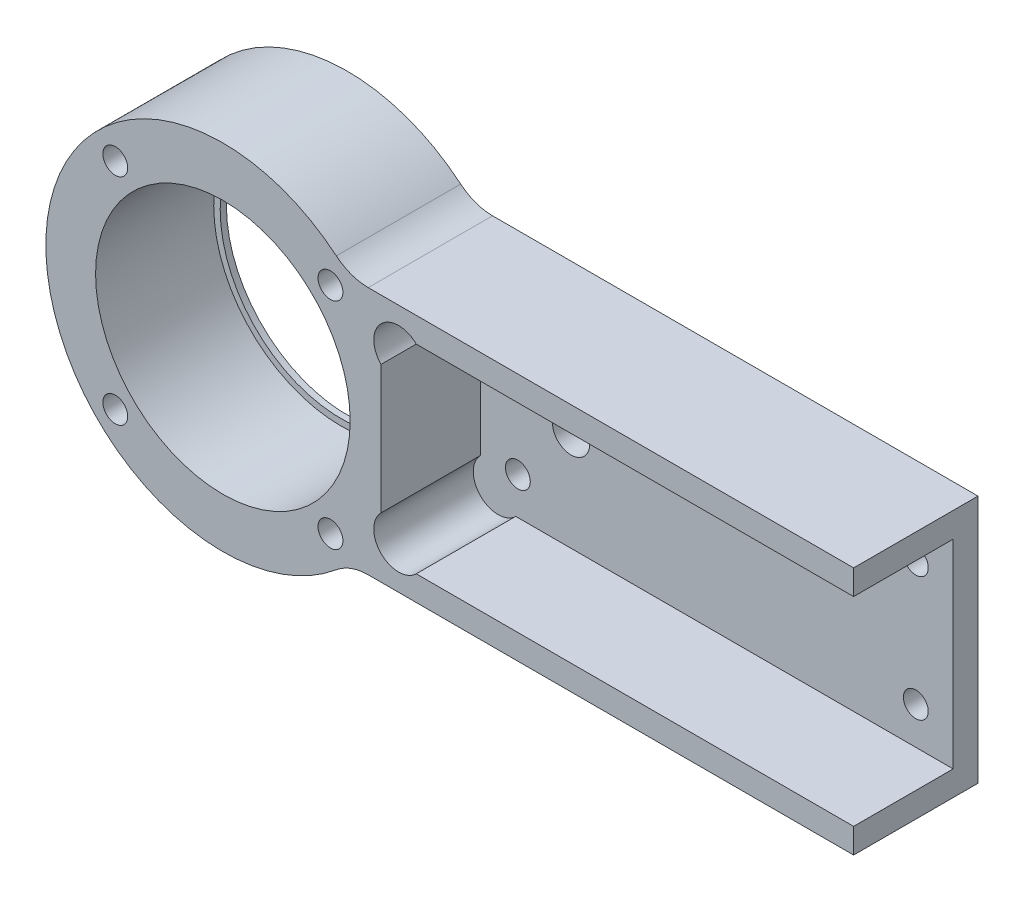
SolidWorks part; units mm, degrees
material "1060 Alloy"
ref_plane "Front Plane" through (0, 0, 0) normal (0, 0, 1) x (1, 0, 0)
ref_plane "Top Plane" through (0, 0, 0) normal (0, 1, 0) x (1, 0, 0)
ref_plane "Right Plane" through (0, 0, 0) normal (1, 0, 0) x (0, 0, -1)
sketch "Sketch1" plane through (0, 0, 0) normal (0, 0, 1) x (1, 0, 0)
  line L0 (32.1711, 31.75) -> (161.036, 31.75)
  line L1 (32.1711, -31.75) -> (161.036, -31.75)
  line L3 (161.036, 31.75) -> (161.036, 25.4)
  line L4 (161.036, -31.75) -> (161.036, -25.4)
  line L5 (161.036, 31.75) -> (161.036, -31.75) construction
  line L6 (161.036, 25.4) -> (40.386, 25.4)
  line L7 (40.386, 25.4) -> (40.386, -25.4)
  line L8 (40.386, -25.4) -> (161.036, -25.4)
  line L9 (161.036, 25.4) -> (161.036, -25.4)
  circle A0 centre (0, 0) radius 32.5
  arc A1 (32.1711, 31.75) -> (32.1711, -31.75) centre (0, 0) ccw
  point P3 (161.036, 0)
  dimension "D1" = 65
  dimension "D4" = 12.7
  dimension "D6" = 40.386
  dimension "D2" = 63.5
  dimension "D3" = 120.65
  dimension "D5" = 6.35
extrude "Boss-Extrude2" add sketch "Sketch1" along normal blind 6.35 contours L0 A1 L1 L4 L8 L7 L6 L3 A0 | L9 L6 L7 L8 region at (33.1354, 0, 0) region at (100.711, 0, 0)
extrude "Boss-Extrude3" add sketch "Sketch1<3>" along normal blind 25.4 from surface contours L0 A1 L1 L4 L8 L7 L6 L3 A0 region at (33.1354, 0, 0) starting at face at (77.2608, 0, 6.35)
sketch "Sketch1<3>" plane through (0, 0, 0) normal (0, 0, 1) x (1, 0, 0) same geometry as "Sketch1"
sketch "Sketch2" plane through (0, 0, 6.35) normal (0, 0, 1) x (1, 0, 0)
  line L0 (161.036, -25.4) -> (161.036, 25.4) construction
  line L1 (40.386, -25.4) -> (40.386, 25.4) construction
  line L2 (-27.4711, 27.4711) -> (0, 0) construction
  line L3 (0, 0) -> (-27.4711, -27.4711) construction
  line L4 (40.386, 25.4) -> (161.036, 25.4) construction
  line L5 (40.386, 25.4) -> (161.036, 25.4) construction
  line L6 (161.036, -25.4) -> (40.386, -25.4) construction
  line L7 (161.036, -25.4) -> (40.386, -25.4) construction
  line L8 (0, 0) -> (27.4711, 27.4711) construction
  line L11 (0, 0) -> (27.4711, -27.4711) construction
  line L13 (0, 0) -> (-32.5, 0) construction
  circle A0 centre (49.911, 15.875) radius 3.175
  circle A1 centre (151.511, 15.875) radius 3.175
  circle A2 centre (151.511, -15.875) radius 3.175
  circle A3 centre (49.911, -15.875) radius 3.175
  circle A4 centre (27.4711, 27.4711) radius 3.175
  circle A5 centre (27.4711, -27.4711) radius 3.175
  circle A6 centre (-27.4711, -27.4711) radius 3.175
  circle A7 centre (-27.4711, 27.4711) radius 3.175
  circle A8 centre (0, 0) radius 32.5 construction
  circle A15 centre (0, 0) radius 38.85 construction
  arc A16 (32.1711, 31.75) -> (32.1711, -31.75) centre (0, 0) ccw construction
  dimension "D1" = 6.35
  dimension "D2" = 6.35
  dimension "D4" = 9.525
  dimension "D5" = 9.525
  dimension "D6" = 9.525
  dimension "D3" = 9.525
  dimension "D7" = 9.525
  dimension "D8" = 9.525
  dimension "D11" = 45
  dimension "D12" = 45
extrude "Cut-Extrude1" cut sketch "Sketch2" against normal through all and the other way through all
sketch "Sketch3" plane through (0, 0, 31.75) normal (0, 0, 1) x (1, 0, 0)
  line L0 (40.386, 25.4) -> (49.3663, 16.4197) construction
  line L1 (40.386, 25.4) -> (161.036, 25.4) construction
  line L2 (40.386, 0) -> (32.5, 0) construction
  line L3 (40.386, -25.4) -> (40.386, 25.4) construction
  circle A0 centre (44.8761, 20.9099) radius 6.35
  circle A1 centre (0, 0) radius 32.5 construction
  circle A2 centre (44.8761, -20.9099) radius 6.35
  dimension "D1" = 12.7
  dimension "D2" = 45
extrude "Cut-Extrude2" cut sketch "Sketch3" against normal up to surface (25.4 mm away) up to face at (53.086, 15.875, 6.35)
sketch "Sketch4" plane through (0, 0, 0) normal (0, 0, -1) x (-1, 0, 0)
  line L0 (-31.75, 54.9926) -> (0, 0) construction
  line L1 (0, 0) -> (31.75, 54.9926) construction
  line L2 (-32.1711, -31.75) -> (-161.036, -31.75) construction
  line L3 (0, 0) -> (63.5, 0) construction
  line L4 (0, 0) -> (31.75, -54.9926) construction
  line L9 (-51.2937, 31.75) -> (-32.1711, 31.75)
  line L10 (-32.1711, 31.75) -> (-161.036, 31.75) construction
  line L11 (-32.1711, -31.75) -> (-51.2937, -31.75)
  line L12 (0, 0) -> (-63.5, 0) construction
  line L13 (0, 0) -> (-31.75, -54.9926) construction
  arc A1 (-40.8506, -48.6156) -> (-40.8506, 48.6156) centre (0, 0) ccw construction
  arc A2 (-20.7603, 56.6402) -> (-38.6717, 46.2991) centre (-31.75, 54.9926) ccw
  arc A8 (38.6717, 46.2991) -> (20.7603, 56.6402) centre (31.75, 54.9926) ccw
  arc A9 (59.432, -10.3411) -> (59.432, 10.3411) centre (63.5, 0) ccw
  arc A10 (20.7603, -56.6402) -> (38.6717, -46.2991) centre (31.75, -54.9926) ccw
  arc A11 (-38.6717, -46.2991) -> (-20.7603, -56.6402) centre (-31.75, -54.9926) ccw
  circle A13 centre (-31.75, 54.9926) radius 4.7625
  arc A14 (-38.6717, 46.2991) -> (-51.2937, 31.75) centre (0, 0) ccw
  circle A15 centre (31.75, 54.9926) radius 4.7625
  arc A16 (-32.1711, -31.75) -> (-32.1711, 31.75) centre (0, 0) ccw construction
  arc A17 (20.7603, 56.6402) -> (-20.7603, 56.6402) centre (0, 0) ccw
  circle A18 centre (63.5, 0) radius 4.7625
  circle A19 centre (31.75, -54.9926) radius 4.7625
  arc A20 (59.432, 10.3411) -> (38.6717, 46.2991) centre (0, 0) ccw
  arc A21 (38.6717, -46.2991) -> (59.432, -10.3411) centre (0, 0) ccw
  circle A22 centre (-31.75, -54.9926) radius 4.7625
  arc A23 (-20.7603, -56.6402) -> (20.7603, -56.6402) centre (0, 0) ccw
  arc A24 (-32.1711, -31.75) -> (-32.1711, 31.75) centre (0, 0) ccw
  arc A25 (-51.2937, -31.75) -> (-38.6717, -46.2991) centre (0, 0) ccw
  circle A26 centre (-63.5, 0) radius 4.7625
  point P48 (0, 0)
  dimension "D1" = 6.35
  dimension "D2" = 127
  dimension "D3" = 6
  dimension "D8" = 60.325
  dimension "D9" = 9.525
extrude "Boss-Extrude5" [suppressed] add sketch "Sketch4" against normal blind 6.35
extrude "Cut-Extrude3" cut sketch "Sketch4<3>" against normal blind 6.35 contours A26 region at (63.5, 0, 0)
sketch "Sketch4<3>" plane through (0, 0, 0) normal (0, 0, -1) x (-1, 0, 0) same geometry as "Sketch4"
fillet "Fillet1" radius 12.7 2 edges at (32.1711, -31.75, 15.875) (32.1711, 31.75, 15.875)
fillet "Fillet2" [suppressed] radius 12.7
sketch "Sketch5" plane through (0, 0, 0) normal (0, 0, -1) x (-1, 0, 0)
  circle A0 centre (0, 0) radius 32.5 construction
  circle A1 centre (0, 0) radius 32.5
  circle A2 centre (0, 0) radius 30.849
  dimension "D1" = 1.651
extrude "Boss-Extrude6" add sketch "Sketch5" against normal blind 1.5875
